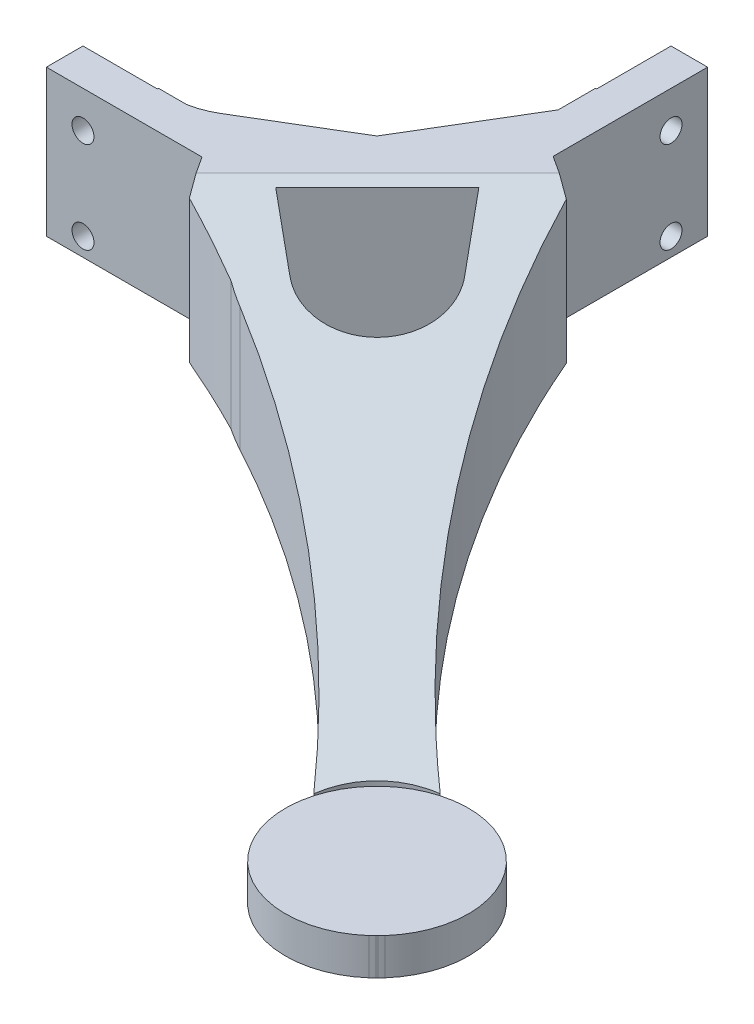
SolidWorks part; units mm, degrees
ref_plane "Front Plane" through (0, 0, 0) normal (0, 0, 1) x (1, 0, 0)
ref_plane "Top Plane" through (0, 0, 0) normal (0, 1, 0) x (1, 0, 0)
ref_plane "Right Plane" through (0, 0, 0) normal (1, 0, 0) x (0, 0, -1)
sketch "Sketch1" plane through (0, 0, 0) normal (0, 1, 0) x (1, 0, 0)
  line L0 (-32.8333, 3.1667) -> (-17.8333, 3.1667)
  line L1 (-17.8333, 3.1667) -> (7.1667, 18.1667)
  line L2 (7.1667, 18.1667) -> (7.1667, 33.1667)
  line L3 (7.1667, 33.1667) -> (12.1667, 33.1667)
  line L4 (12.1667, 33.1667) -> (12.1667, 18.1667)
  line L8 (-7.8333, -1.8333) -> (-32.8333, -1.8333)
  line L9 (-32.8333, -1.8333) -> (-32.8333, 3.1667)
  line L11 (12.1667, 18.1667) -> (17.5272, 18.1667)
  line L12 (-7.8333, -1.8333) -> (-7.8333, -7.1938)
  arc A0 (56.4946, -55.8323) -> (66.1657, -46.1613) centre (65.8063, -55.4729) ccw
  arc A1 (56.4946, -55.8323) -> (-7.8333, -7.1938) centre (-62.8059, -146.7575) ccw
  arc A2 (17.5272, 18.1667) -> (66.1657, -46.1613) centre (157.0908, 73.1392) ccw
  dimension "D1" = 15
  dimension "D2" = 5
  dimension "D3" = 15
  dimension "D4" = 5
  dimension "D5" = 25
  dimension "D6" = 25
  dimension "D7" = 15
  dimension "D8" = 15
  dimension "D11" = 155
  dimension "D14" = 155
extrude "Boss-Extrude3" add sketch "Sketch1" along normal blind 25
chamfer "Chamfer2" distance 6 angle 33 2 edges at (-7.8333, 12.5, 7.1938) (17.5272, 12.5, -18.1667) first distance on face at (-7.8333, 12.5, 4.5136) first distance on face at (39.6443, 12.5, 15.6623)
fillet "Fillet2" radius 30 2 edges at (19.7268, 12.5, -12.8805) (-2.8836, 12.5, 9.2464)
sketch "Sketch2" plane through (0, 0, 1.8333) normal (0, 0, 1) x (1, 0, 0)
  line L0 (-32.8333, 0) -> (-7.5027, 0) construction
  circle A0 centre (-27.8333, 20) radius 1.5
  circle A1 centre (-27.8333, 7.5) radius 1.5
  dimension "D1" = 20
  dimension "D3" = 12.5
  dimension "D2" = 35
extrude "Cut-Extrude1" cut sketch "Sketch2" against normal blind 25
sketch "Sketch3" plane through (12.1667, 0, 0) normal (1, 0, 0) x (0, 0, -1)
  line L0 (18.0687, 25) -> (33.1667, 25) construction
  circle A0 centre (28.1667, 20) radius 1.5
  circle A1 centre (28.1667, 7.5) radius 1.5
  dimension "D1" = 25
  dimension "D3" = 12.5
  dimension "D2" = 5
extrude "Cut-Extrude2" cut sketch "Sketch3" against normal blind 25
sketch "Sketch4" plane through (0, 25, 0) normal (0, 1, 0) x (1, 0, 0)
  line L0 (17.1652, 5.2091) -> (10.4484, 13.8698)
  line L1 (10.4484, 13.8698) -> (-3.4214, 0)
  line L2 (-3.4214, 0) -> (5.2393, -6.7168)
  arc A0 (56.4946, -55.8323) -> (4.4419, -12.6764) centre (-62.8059, -146.7575) ccw construction
  arc A1 (22.8804, 6.15) -> (66.1657, -46.1613) centre (157.0908, 73.1392) ccw construction
  arc A2 (22.8804, 6.15) -> (66.1657, -46.1613) centre (157.0908, 73.1392) ccw construction
  arc A4 (5.2393, -6.7168) -> (17.1652, 5.2091) centre (10.4484, 0) ccw
  point P4 (32.9316, -31.2832)
  point P10 (41.5243, -22.487)
  point P14 (32.9316, -31.2832)
  point P15 (41.5243, -22.487)
extrude "Cut-Extrude4" cut sketch "Sketch4" against normal blind 25
fillet "Fillet3" radius 6 2 edges at (10.4484, 12.5, -13.8698) (-3.4214, 12.5, 0)
sketch "Sketch7" plane through (0, 25, 0) normal (0, 1, 0) x (1, 0, 0)
  line L0 (8.9535, 27.4642) -> (42.7588, -6.3411)
  line L1 (42.7588, -6.3411) -> (46.7756, -2.3243)
  line L2 (46.7756, -2.3243) -> (12.9703, 31.481)
  line L3 (12.9703, 31.481) -> (8.9535, 27.4642)
extrude "Boss-Extrude4" add sketch "Sketch7" along normal blind 25
sketch "Sketch10" plane through (22.2256, 0, -22.2256) normal (0.7071, 0, -0.7071) x (-0.7071, 0, -0.7071)
  line L0 (-95.076, 0) -> (-95.076, 5)
  line L1 (-95.076, 25) -> (-95.076, 0) construction
  line L2 (-95.076, 5) -> (-72.576, 5)
  line L3 (-72.576, 5) -> (4.1734, 25)
  line L4 (4.1734, 25) -> (18.3848, 25)
  line L5 (18.3848, 25) -> (25.4558, 25)
  line L6 (18.3848, 25) -> (18.3848, 0) construction
  line L7 (18.3848, 5) -> (4.1734, 5)
  line L8 (4.1734, 25) -> (4.1734, 0) construction
  line L9 (4.1734, 5) -> (-65.076, 0)
  line L10 (-79.4271, 0) -> (-11.8302, 0) construction
  line L11 (-65.076, 0) -> (-95.076, 0)
  line L12 (25.4558, 25) -> (25.4558, 5)
  line L13 (-116.8035, -30.6808) -> (43.3804, -30.6808)
  line L14 (-116.8035, -30.6808) -> (-116.8035, 52.4335)
  line L15 (-116.8035, 52.4335) -> (43.3804, 52.4335)
  line L16 (43.3804, -30.6808) -> (43.3804, 52.4335)
  line L17 (25.4558, 25) -> (25.4558, 0) construction
  line L18 (25.4558, 5) -> (18.3848, 5)
  dimension "D1" = 22.5
  dimension "D2" = 30
  dimension "D3" = 5
  dimension "D4" = 20
extrude "Cut-Extrude6" cut sketch "Sketch10" against normal blind 100 and the other way blind 100
sketch "Sketch11" plane through (0, 5, 0) normal (0, 1, 0) x (1, 0, 0)
  circle A0 centre (63.6345, -53.1462) radius 12.5
  arc A1 (56.4946, -55.8323) -> (66.1657, -46.1613) centre (65.8063, -55.4729) ccw construction
  point P2 (72.3955, -62.0622)
  dimension "D1" = 12.5
extrude "Boss-Extrude5" add sketch "Sketch11" against normal up to surface (5 mm away) up to face at (59.0278, 0, 48.6945)
sketch "Sketch12" plane through (0, 5, 0) normal (0, 1, 0) x (1, 0, 0)
  circle A0 centre (63.6345, -53.1462) radius 12.5
extrude "Cut-Extrude7" cut sketch "Sketch12" along normal blind 100
fillet "Fillet5" radius 10 2 edges at (-17.8333, 15, -3.1667) (7.1667, 15, -18.1667)
sketch "Sketch13" plane through (0, 25, 0) normal (0, 1, 0) x (1, 0, 0)
  line L0 (63.6345, -53.1462) -> (-2.1115, 12.5998)
  line L1 (2.3116, 15.2536) -> (-15.4582, 4.5917) construction
  line L2 (-2.1115, 12.5998) -> (-4.7886, 9.9227)
  line L3 (-4.7886, 9.9227) -> (60.9574, -55.8233)
  line L4 (60.9574, -55.8233) -> (63.6345, -53.1462)
extrude "Boss-Extrude6" add sketch "Sketch13" along normal blind 6
mirror "Mirror2" about plane through (63.6345, 31, 53.1462) normal (-0.7071, 0, 0.7071) of "Boss-Extrude3", "Cut-Extrude1", "Cut-Extrude2", "Cut-Extrude6", "Cut-Extrude4", "Boss-Extrude5", "Cut-Extrude7"
chamfer "Chamfer3" distance 6 angle 33 2 edges at (-7.6784, 14.9933, 1.8333) (12.3216, 15, -18.3216) first distance on face at (-7.6784, 14.687, 4.4361) first distance on face at (14.1411, 14.7936, -18.3216)
